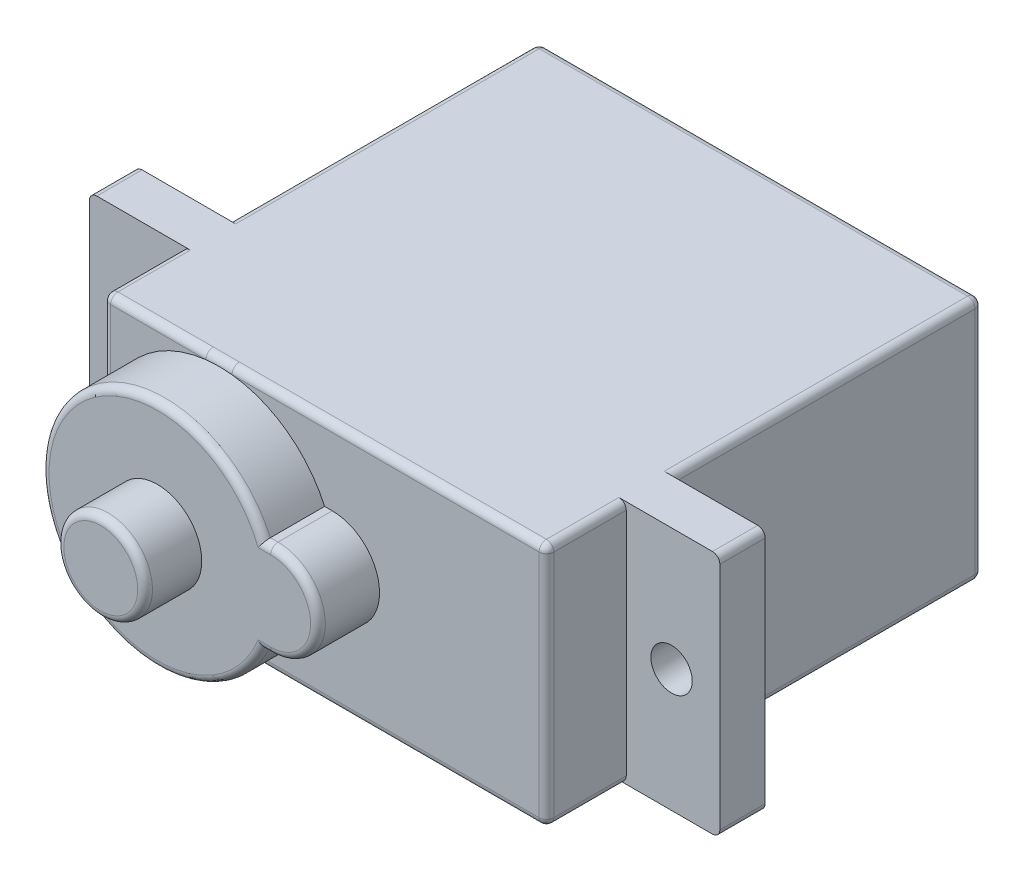
SolidWorks part; units mm, degrees
ref_plane "Front Plane" through (0, 0, 0) normal (0, 0, 1) x (1, 0, 0)
ref_plane "Top Plane" through (0, 0, 0) normal (0, 1, 0) x (1, 0, 0)
ref_plane "Right Plane" through (0, 0, 0) normal (1, 0, 0) x (0, 0, -1)
sketch "Sketch1" plane through (0, 0, 0) normal (0, 0, 1) x (1, 0, 0)
  line L1 (0, 0) -> (22.86, 0)
  line L2 (0, 0) -> (0, 12.6238)
  line L3 (0, 12.6238) -> (22.86, 12.6238)
  line L4 (22.86, 0) -> (22.86, 12.6238)
  dimension "D1" = 22.86
  dimension "D2" = 12.6238
extrude "Boss-Extrude1" add sketch "Sketch1" along normal blind 22.479
sketch "Sketch2" plane through (0, 0, 22.479) normal (0, 0, 1) x (1, 0, 0)
  line L0 (0, 6.3119) -> (10.3369, 6.3119) construction
  line L1 (0, 12.6238) -> (0, 0) construction
  line L2 (11.811, 8.7503) -> (11.4172, 8.7503)
  line L3 (11.811, 3.8735) -> (11.4172, 3.8735)
  arc A0 (11.4172, 8.7503) -> (11.4172, 3.8735) centre (5.969, 6.3119) ccw
  arc A1 (11.811, 3.8735) -> (11.811, 8.7503) centre (11.811, 6.3119) ccw
  dimension "D1" = 11.938
  dimension "D4" = 4.8768
  dimension "D2" = 5.969
  dimension "D3" = 5.842
extrude "Boss-Extrude2" add sketch "Sketch2" along normal blind 3.175
sketch "Sketch3" plane through (0, 0, 25.654) normal (0, 0, 1) x (1, 0, 0)
  circle A0 centre (5.969, 6.3119) radius 2.286
  dimension "D1" = 4.572
extrude "Boss-Extrude3" add sketch "Sketch3" along normal blind 2.921
ref_plane "Plane1" through (0, 0, 16.0274) normal (0, 0, -1) x (-1, 0, 0)
sketch "Sketch4" plane through (0, 0, 16.0274) normal (0, 0, -1) x (-1, 0, 0)
  line L0 (-22.86, 12.6238) -> (-27.686, 12.6238)
  line L1 (-27.686, 12.6238) -> (-27.686, 0)
  line L2 (-27.686, 0) -> (-22.86, 0)
  line L3 (-22.86, 0) -> (-22.86, 12.6238)
  line L5 (0, 12.6238) -> (4.826, 12.6238)
  line L6 (0, 12.6238) -> (0, 0)
  line L7 (0, 0) -> (4.826, 0)
  line L8 (4.826, 12.6238) -> (4.826, 0)
  dimension "D1" = 4.826
  dimension "D2" = 4.826
extrude "Boss-Extrude4" add sketch "Sketch4" against normal blind 2.3368
fillet "Fillet1" radius 0.381 26 edges at (0, 9.4678, 22.479) (0, 3.1559, 22.479) (8.255, 6.3119, 28.575) (0, 6.3119, 25.654) (0, 6.3119, 0) (11.43, 0, 0) (22.86, 6.3119, 0) (11.43, 12.6238, 0) (0, 12.6238, 8.0137) (0, 12.6238, 20.4216) (0, 0, 20.4216) (0, 0, 8.0137) (22.86, 6.3119, 22.479) (11.43, 12.6238, 22.479) (11.43, 0, 22.479) (27.686, 12.6238, 17.1958) (27.686, 0, 17.1958) (-4.826, 0, 17.1958) (-4.826, 12.6238, 17.1958) (11.6141, 3.8735, 25.654) (11.6141, 8.7503, 25.654) (14.2494, 6.3119, 25.654)
sketch "Sketch6" plane through (0, 0, 18.3642) normal (0, 0, 1) x (1, 0, 0)
  line L0 (-4.826, 6.3119) -> (27.686, 6.3119) construction
  line L1 (-4.826, 0.381) -> (-4.826, 12.2428) construction
  line L2 (27.686, 12.2428) -> (27.686, 0.381) construction
  circle A0 centre (-2.3368, 6.3119) radius 1.0668
  circle A1 centre (25.1968, 6.3119) radius 1.0668
  dimension "D1" = 2.1336
  dimension "D2" = 30.0228
  dimension "D3" = 30.0228
extrude "Cut-Extrude1" cut sketch "Sketch6" against normal through all
